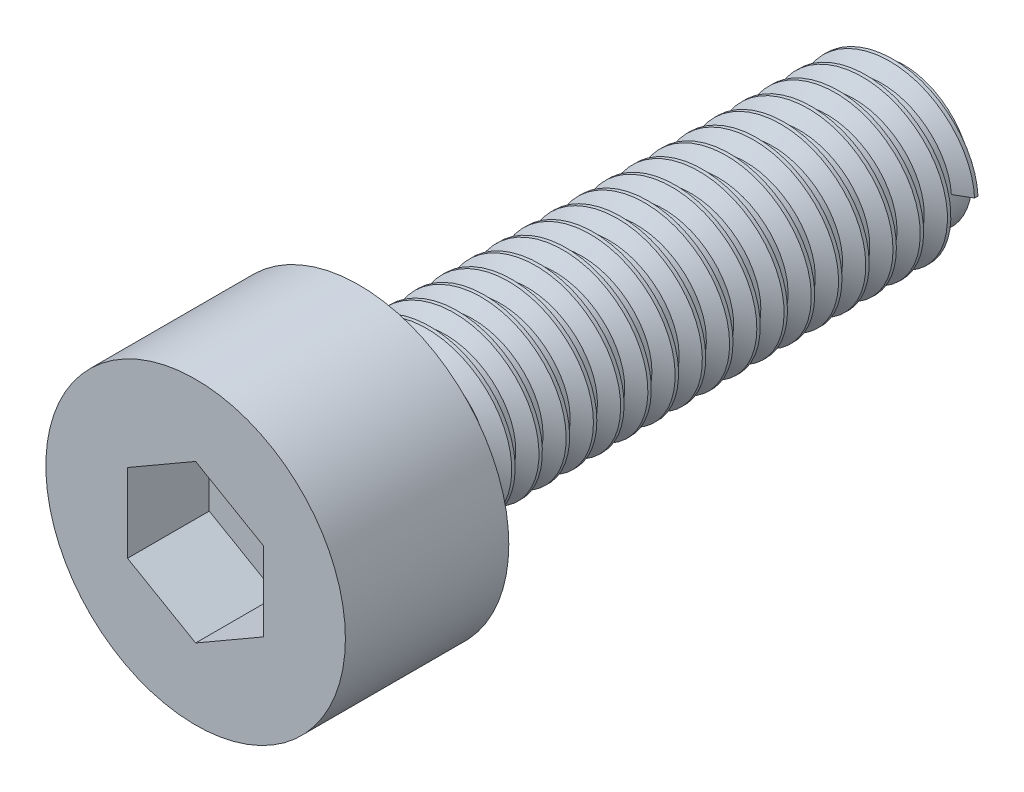
SolidWorks part; units mm, degrees
material "Cast Carbon Steel"
ref_plane "Front Plane" through (0, 0, 0) normal (0, 0, 1) x (1, 0, 0)
ref_plane "Top Plane" through (0, 0, 0) normal (0, 1, 0) x (1, 0, 0)
ref_plane "Right Plane" through (0, 0, 0) normal (1, 0, 0) x (0, 0, -1)
sketch "Sketch1" plane through (0, 0, 0) normal (0, 0, 1) x (1, 0, 0)
  circle A0 centre (0, 0) radius 2.75
  dimension "D1" = 5.5
extrude "Boss-Extrude1" add sketch "Sketch1" along normal blind 3
sketch "Sketch2" plane through (0, 0, 0) normal (0, 0, -1) x (-1, 0, 0)
  circle A0 centre (0, 0) radius 1.25
  dimension "D1" = 2.5
extrude "Boss-Extrude2" add sketch "Sketch2" along normal blind 10
sketch "Sketch3" plane through (0, 0, 3) normal (0, 0, 1) x (1, 0, 0)
  line L1 (0, 1.4434) -> (-1.25, 0.7217)
  line L2 (-1.25, 0.7217) -> (-1.25, -0.7217)
  line L3 (-1.25, -0.7217) -> (0, -1.4434)
  line L4 (0, -1.4434) -> (1.25, -0.7217)
  line L5 (1.25, -0.7217) -> (1.25, 0.7217)
  line L6 (1.25, 0.7217) -> (0, 1.4434)
  circle A0 centre (0, 0) radius 1.25 construction
  dimension "D1" = 2.5
extrude "Cut-Extrude1" cut sketch "Sketch3" against normal blind 1.5
thread "Thread1" pitch 0.5 method extrude profile "Thread Profile1" start angle 0, offset 0, length 10, pitch 0.5, diameter 2.5
ref_plane "Plane1" through (1.25, 0, -10) normal (0, -1, 0) x (1, 0, 0)
sketch "Thread Profile1" plane through (1.25, 0, -10) normal (0, -1, 0) x (1, 0, 0)
  line L0 (0, 0) -> (0, 0.5) construction
  line L1 (0, 0) -> (0.2706, 0.1562)
  line L2 (0.2706, 0.1562) -> (0.2706, 0.2187)
  line L3 (0.2706, 0.2187) -> (0, 0.375)
  line L4 (0.2706, 0.1875) -> (0, 0.1875) construction
  line L11 (0, 0) -> (0, 0.375)
  point P2 (0, 0)
  dimension "Pitch" = 0.5
  dimension "Profile_Angle" = 60
  dimension "Profile_Land" = 0.0625
  dimension "Profile_Height" = 0.2706
